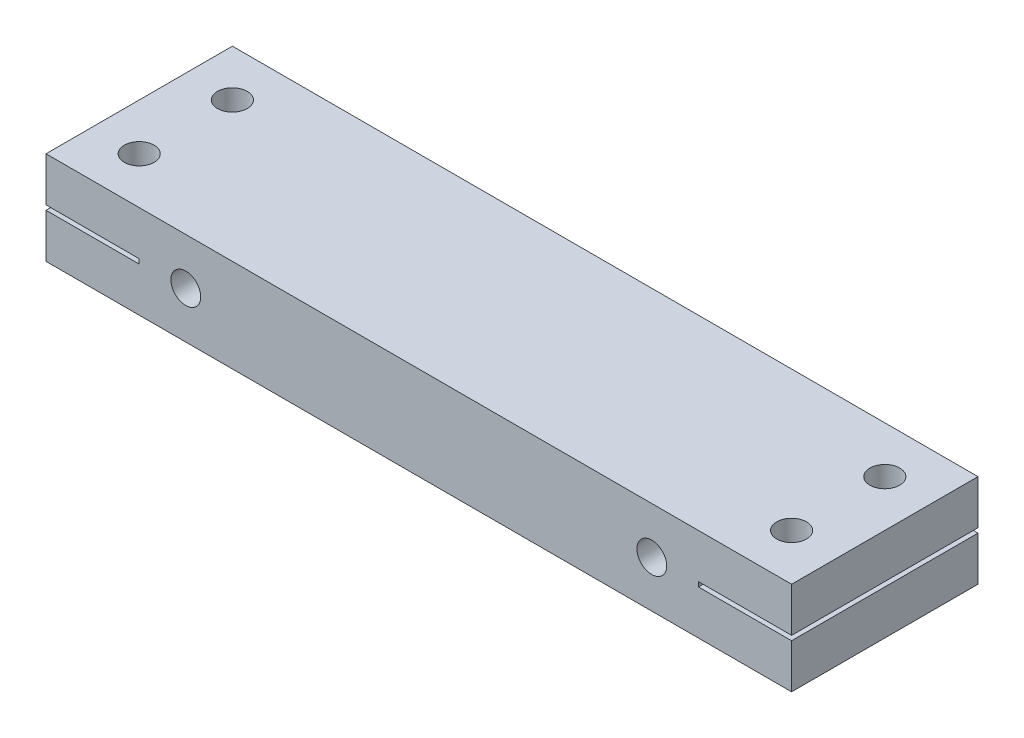
SolidWorks part; units mm, degrees
ref_plane "Front Plane" through (0, 0, 0) normal (0, 0, 1) x (1, 0, 0)
ref_plane "Top Plane" through (0, 0, 0) normal (0, 1, 0) x (1, 0, 0)
ref_plane "Right Plane" through (0, 0, 0) normal (1, 0, 0) x (0, 0, -1)
sketch "Sketch1" plane through (0, 0, 0) normal (0, 0, 1) x (1, 0, 0)
  line L0 (0, -5) -> (80, -5)
  line L1 (80, -5) -> (80, 5)
  line L2 (80, 5) -> (0, 5)
  line L3 (0, 5) -> (0, -5)
  point P6 (0, 0)
  dimension "D1" = 80
  dimension "D2" = 10
extrude "Boss-Extrude1" add sketch "Sketch1" along normal mid plane 20
sketch "Sketch2" plane through (0, 0, 10) normal (0, 0, 1) x (1, 0, 0)
  line L0 (0, 5) -> (0, -5) construction
  line L1 (0, 0.25) -> (10, 0.25)
  line L2 (0, 0.25) -> (0, -0.25)
  line L3 (0, -0.25) -> (10, -0.25)
  line L4 (10, 0.25) -> (10, -0.25)
  line L5 (80, -5) -> (80, 5) construction
  line L6 (80, 0.25) -> (70, 0.25)
  line L7 (80, 0.25) -> (80, -0.25)
  line L8 (80, -0.25) -> (70, -0.25)
  line L9 (70, 0.25) -> (70, -0.25)
  line L10 (80, 5) -> (0, 5) construction
  line L11 (0, 0.25) -> (0, -0.25)
  line L12 (80, 0.25) -> (80, -0.25)
  point P12 (10, 0)
  line M9 (0, 5) -> (0, -5)
  line M11 (80, -5) -> (80, 5)
  dimension "D1" = 5
  dimension "D2" = 0.5
  dimension "D3" = 10
extrude "Cut-Extrude1" cut sketch "Sketch2" against normal through all contours L4 L1 L3 M9 | L6 L9 L8 M11 region at (5, 0, 10) region at (75, 0, 10)
sketch "Sketch3" plane through (0, 5, 0) normal (0, 1, 0) x (1, 0, 0)
  line L0 (0, 0) -> (80, 0) construction
  line L1 (0, -10) -> (0, 10) construction
  line L2 (80, -10) -> (80, 10) construction
  line L3 (40, -10) -> (40, 10) construction
  line L4 (80, -10) -> (0, -10) construction
  line L5 (80, 10) -> (0, 10) construction
  circle A0 centre (5, 5) radius 1.6
  circle A1 centre (75, 5) radius 1.6
  circle A2 centre (5, -5) radius 1.6
  circle A3 centre (75, -5) radius 1.6
  point P16 (5, 4.7682)
  point P17 (0, 0)
  point P20 (5, -5.7547)
  point P23 (75, -5.7547)
  point P24 (0, 0)
  point P25 (0, 0)
  point P26 (5, -5)
  dimension "D1" = 5
  dimension "D2" = 3.2
  dimension "D3" = 5
extrude "Cut-Extrude2" cut sketch "Sketch3" against normal through all
sketch "Sketch4" plane through (0, 0, 0) normal (0, 0, 1) x (1, 0, 0)
  line L0 (0, 5) -> (0, 0) construction
  line L2 (0, 0) -> (80, 0) construction
  line L4 (80, 0) -> (90, 0) construction
  line L5 (0, 0) -> (-10, 0) construction
  line L6 (80, 0.25) -> (80, 5) construction
  circle A0 centre (-10, 0) radius 10 construction
  circle A1 centre (90, 0) radius 10 construction
  dimension "D2" = 10
  dimension "D1" = 20
sketch "Sketch5" plane through (0, 0, 10) normal (0, 0, 1) x (1, 0, 0)
  line L0 (0, 5) -> (0, 0.25) construction
  line L1 (0, 0) -> (15, 0) construction
  line L2 (15, 0) -> (65, 0) construction
  line L3 (80, 0.25) -> (80, 5) construction
  circle A0 centre (15, 0) radius 1.6
  circle A1 centre (65, 0) radius 1.6
  dimension "D1" = 3.2
  dimension "D2" = 15
  dimension "D3" = 15
extrude "Cut-Extrude3" cut sketch "Sketch5" against normal through all
equation "\"Leg_length\"= 80"
equation "\"D1@Sketch1\"=\"Leg_length\""
equation "\"Leg_width\"=10"
equation "\"D2@Sketch1\"=\"Leg_width\""
equation "\"D1@Sketch2\"=\"Leg_width\"/2"
equation "\"Leaf_Spring_Thickness\"= 0.5"
equation "\"D2@Sketch2\"=\"Leaf_Spring_Thickness\""
equation "\"Leaf_Spring_Slot_Depth\"=10"
equation "\"D3@Sketch2\"=\"Leaf_Spring_Slot_Depth\""
equation "\"D1@Sketch3\"=\"Leaf_Spring_Slot_Depth\"/2"
equation "\"Leaf_Spring_Radii\"=10"
equation "\"D2@Sketch4\"=\"Leaf_Spring_Radii\""
